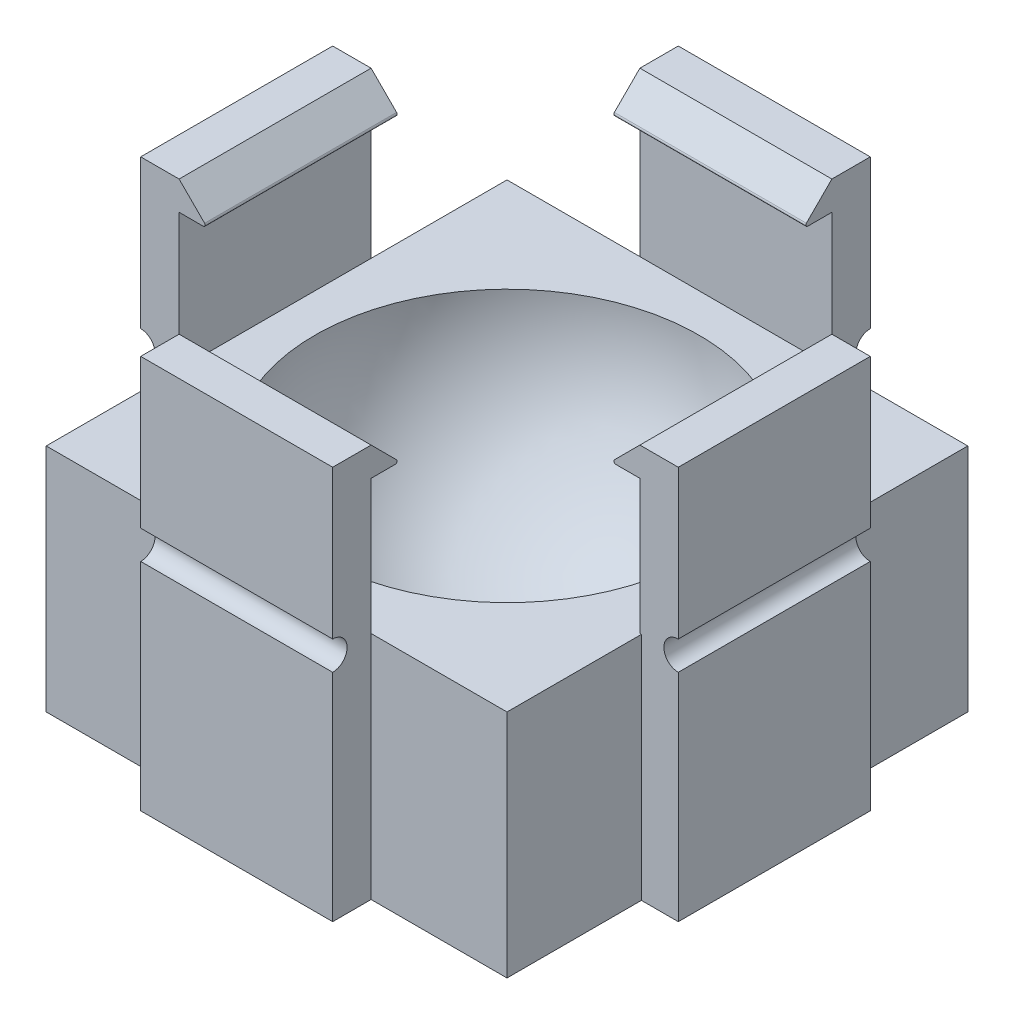
SolidWorks part; units mm, degrees
ref_plane "Front Plane" through (0, 0, 0) normal (0, 0, 1) x (1, 0, 0)
ref_plane "Top Plane" through (0, 0, 0) normal (0, 1, 0) x (1, 0, 0)
ref_plane "Right Plane" through (0, 0, 0) normal (1, 0, 0) x (0, 0, -1)
sketch "Sketch1" plane through (0, 0, 0) normal (0, 1, 0) x (1, 0, 0)
  line L1 (0, 0) -> (250, 0)
  line L2 (0, 0) -> (0, 250)
  line L3 (0, 250) -> (250, 250)
  line L4 (250, 0) -> (250, 250)
  dimension "D1" = 250
  dimension "D2" = 250
extrude "Boss-Extrude1" add sketch "Sketch1" along normal blind 5
sketch "Sketch2" plane through (0, 5, 0) normal (0, 1, 0) x (1, 0, 0)
  line L1 (113, 113) -> (137, 113)
  line L2 (113, 113) -> (113, 137)
  line L3 (113, 137) -> (137, 137)
  line L4 (137, 113) -> (137, 137)
  line L5 (113, 113) -> (137, 137) construction
  line L6 (113, 137) -> (137, 113) construction
  line L7 (0, 250) -> (0, 0) construction
  line L8 (250, 250) -> (0, 250) construction
  line L10 (221, 137) -> (221, 113)
  line L11 (221, 113) -> (245, 113)
  line L12 (245, 113) -> (245, 137)
  line L13 (245, 137) -> (221, 137)
  line L19 (137, 29.0789) -> (113, 29.0789)
  line L20 (113, 29.0789) -> (113, 5.0789)
  line L21 (113, 5.0789) -> (137, 5.0789)
  line L22 (137, 5.0789) -> (137, 29.0789)
  point P0 (125, 125)
  dimension "D1" = 24
  dimension "D2" = 24
  dimension "D3" = 125
  dimension "D4" = 125
extrude "Boss-Extrude2" add sketch "Sketch2" along normal blind 12
sketch "Sketch4" plane through (0, 17, 0) normal (0, 1, 0) x (1, 0, 0)
  line L0 (125, 135) -> (125, 115)
  line L1 (125, 7) -> (125, 27)
  line L3 (233, 135) -> (233, 115)
  arc A0 (125, 135) -> (125, 115) centre (125, 125) ccw
  arc A2 (125, 27) -> (125, 7) centre (125, 17) ccw
  arc A3 (233, 115) -> (233, 135) centre (233, 125) ccw
revolve "Cut-Revolve1" cut sketch "Sketch4" angle 360 about L0 region at (120.7559, 17, -125)
revolve "Cut-Revolve2" cut sketch "Sketch4<3>" angle 360 about L3
sketch "Sketch4<3>" plane through (0, 17, 0) normal (0, 1, 0) x (1, 0, 0) same geometry as "Sketch4"
revolve "Cut-Revolve3" cut sketch "Sketch4<4>" angle 360 about L1
sketch "Sketch4<4>" plane through (0, 17, 0) normal (0, 1, 0) x (1, 0, 0) same geometry as "Sketch4"
sketch "Sketch5" plane through (0, 5, 0) normal (0, 1, 0) x (1, 0, 0)
  line L8 (125, 137) -> (130, 137)
  line L9 (137, 137) -> (113, 137) construction
  line L10 (137, 137) -> (113, 137) construction
  line L11 (130, 137) -> (130, 139)
  line L12 (130, 139) -> (120, 139)
  line L13 (120, 139) -> (120, 137)
  line L14 (120, 137) -> (125, 137)
  line L15 (120, 113) -> (125, 113)
  line L16 (120, 111) -> (120, 113)
  line L17 (130, 111) -> (120, 111)
  line L18 (130, 113) -> (130, 111)
  line L19 (125, 113) -> (130, 113)
  line L21 (113, 29.0789) -> (113, 5.0789) construction
  line L22 (137, 5.0789) -> (137, 29.0789) construction
  line L24 (125, 29.0789) -> (130, 29.0789)
  line L25 (130, 29.0789) -> (130, 31.0789)
  line L26 (130, 31.0789) -> (120, 31.0789)
  line L27 (120, 31.0789) -> (120, 29.0789)
  line L28 (120, 29.0789) -> (125, 29.0789)
  line L29 (120, 5.0789) -> (125, 5.0789)
  line L30 (120, 3.0789) -> (120, 5.0789)
  line L31 (130, 3.0789) -> (120, 3.0789)
  line L32 (130, 5.0789) -> (130, 3.0789)
  line L33 (125, 5.0789) -> (130, 5.0789)
  line L36 (113, 130) -> (113, 125)
  line L37 (111, 130) -> (113, 130)
  line L38 (111, 120) -> (111, 130)
  line L39 (113, 120) -> (111, 120)
  line L40 (113, 125) -> (113, 120)
  line L41 (137, 125) -> (137, 120)
  line L42 (137, 120) -> (139, 120)
  line L43 (139, 120) -> (139, 130)
  line L44 (139, 130) -> (137, 130)
  line L45 (137, 130) -> (137, 125)
  line L46 (220.9211, 130) -> (220.9211, 125)
  line L47 (218.9211, 130) -> (220.9211, 130)
  line L48 (218.9211, 120) -> (218.9211, 130)
  line L49 (220.9211, 120) -> (218.9211, 120)
  line L50 (220.9211, 125) -> (220.9211, 120)
  line L51 (244.9211, 125) -> (244.9211, 120)
  line L52 (244.9211, 120) -> (246.9211, 120)
  line L53 (246.9211, 120) -> (246.9211, 130)
  line L54 (246.9211, 130) -> (244.9211, 130)
  line L55 (244.9211, 130) -> (244.9211, 125)
  line L56 (137, 12.0789) -> (137, 17.0789)
  line L57 (139, 12.0789) -> (137, 12.0789)
  line L58 (139, 22.0789) -> (139, 12.0789)
  line L59 (137, 22.0789) -> (139, 22.0789)
  line L60 (137, 17.0789) -> (137, 22.0789)
  line L61 (113, 17.0789) -> (113, 22.0789)
  line L62 (113, 22.0789) -> (111, 22.0789)
  line L63 (111, 22.0789) -> (111, 12.0789)
  line L64 (111, 12.0789) -> (113, 12.0789)
  line L65 (113, 12.0789) -> (113, 17.0789)
  line L66 (237.9211, 137) -> (232.9211, 137)
  line L67 (237.9211, 139) -> (237.9211, 137)
  line L68 (227.9211, 139) -> (237.9211, 139)
  line L69 (227.9211, 137) -> (227.9211, 139)
  line L70 (232.9211, 137) -> (227.9211, 137)
  line L71 (232.9211, 113) -> (227.9211, 113)
  line L72 (227.9211, 113) -> (227.9211, 111)
  line L73 (227.9211, 111) -> (237.9211, 111)
  line L74 (237.9211, 111) -> (237.9211, 113)
  line L75 (237.9211, 113) -> (232.9211, 113)
extrude "Boss-Extrude3" add sketch "Sketch5" along normal blind 19
sketch "Sketch8" plane through (120, 0, 0) normal (-1, 0, 0) x (0, 0, 1)
  line L0 (-3.0789, 24) -> (-6.5789, 24)
  line L1 (-3.0789, 24) -> (-3.0789, 25.5)
  line L2 (-3.0789, 25.5) -> (-5.0789, 25.5)
  line L3 (-5.0789, 25.5) -> (-6.5789, 24)
  line L8 (-29.0789, 25.5) -> (-27.5789, 24)
  line L9 (-31.0789, 25.5) -> (-29.0789, 25.5)
  line L10 (-31.0789, 24) -> (-31.0789, 25.5)
  line L11 (-31.0789, 24) -> (-27.5789, 24)
  line L12 (-111, 24) -> (-114.5, 24)
  line L13 (-111, 24) -> (-111, 25.5)
  line L14 (-111, 25.5) -> (-113, 25.5)
  line L15 (-113, 25.5) -> (-114.5, 24)
  line L16 (-137, 25.5) -> (-135.5, 24)
  line L17 (-139, 25.5) -> (-137, 25.5)
  line L18 (-139, 24) -> (-139, 25.5)
  line L19 (-139, 24) -> (-135.5, 24)
extrude "Boss-Extrude5" add sketch "Sketch8" against normal blind 10
sketch "Sketch9" plane through (0, 0, -130) normal (0, 0, -1) x (-1, 0, 0)
  line L0 (-111, 24) -> (-114.5, 24)
  line L1 (-111, 24) -> (-111, 25.5)
  line L2 (-111, 25.5) -> (-113, 25.5)
  line L3 (-113, 25.5) -> (-114.5, 24)
  line L8 (-137, 25.5) -> (-135.5, 24)
  line L9 (-139, 25.5) -> (-137, 25.5)
  line L10 (-139, 24) -> (-139, 25.5)
  line L11 (-139, 24) -> (-135.5, 24)
  line L12 (-218.9211, 24) -> (-222.4211, 24)
  line L13 (-218.9211, 24) -> (-218.9211, 25.5)
  line L14 (-218.9211, 25.5) -> (-220.9211, 25.5)
  line L15 (-220.9211, 25.5) -> (-222.4211, 24)
  line L16 (-244.9211, 25.5) -> (-243.4211, 24)
  line L17 (-246.9211, 25.5) -> (-244.9211, 25.5)
  line L18 (-246.9211, 24) -> (-246.9211, 25.5)
  line L19 (-246.9211, 24) -> (-243.4211, 24)
extrude "Boss-Extrude6" add sketch "Sketch9" against normal blind 10
sketch "Sketch10" plane through (237.9211, 0, 0) normal (1, 0, 0) x (0, 0, -1)
  line L0 (139, 24) -> (135.5, 24)
  line L1 (135.5, 24) -> (137, 25.5)
  line L2 (137, 25.5) -> (139, 25.5)
  line L3 (139, 25.5) -> (139, 24)
  line L8 (111, 25.5) -> (111, 24)
  line L9 (113, 25.5) -> (111, 25.5)
  line L10 (114.5, 24) -> (113, 25.5)
  line L11 (111, 24) -> (114.5, 24)
extrude "Boss-Extrude7" add sketch "Sketch10" against normal blind 10
sketch "Sketch11" plane through (0, 0, -12.0789) normal (0, 0, 1) x (1, 0, 0)
  line L0 (139, 24) -> (135.5, 24)
  line L1 (135.5, 24) -> (137, 25.5)
  line L2 (137, 25.5) -> (139, 25.5)
  line L3 (139, 25.5) -> (139, 24)
  line L6 (111, 25.5) -> (111, 24)
  line L7 (113, 25.5) -> (111, 25.5)
  line L8 (114.5, 24) -> (113, 25.5)
  line L9 (111, 24) -> (114.5, 24)
extrude "Boss-Extrude8" add sketch "Sketch11" against normal blind 10
sketch "Sketch12" plane through (0, 0, -12.0789) normal (0, 0, 1) x (1, 0, 0)
  line L0 (139, 25.5) -> (139, 5) construction
  line L1 (111, 25.5) -> (111, 5) construction
  circle A0 centre (139, 17) radius 0.75
  circle A1 centre (111, 17) radius 0.75
extrude "Cut-Extrude1" cut sketch "Sketch12" against normal through all
sketch "Sketch13" plane through (120, 0, 0) normal (-1, 0, 0) x (0, 0, 1)
  line L0 (-111, 25.5) -> (-111, 5) construction
  line L1 (-139, 25.5) -> (-139, 5) construction
  circle A0 centre (-111, 17) radius 0.75
  circle A1 centre (-139, 17) radius 0.75
extrude "Cut-Extrude2" cut sketch "Sketch13" against normal through all
sketch "Sketch14" plane through (0, 0, -130) normal (0, 0, -1) x (-1, 0, 0)
  line L0 (-218.9211, 25.5) -> (-218.9211, 5) construction
  line L1 (-246.9211, 25.5) -> (-246.9211, 5) construction
  circle A0 centre (-218.9211, 17) radius 0.75
  circle A1 centre (-246.9211, 17) radius 0.75
extrude "Cut-Extrude3" cut sketch "Sketch14" against normal through all
sketch "Sketch15" plane through (130, 0, 0) normal (1, 0, 0) x (0, 0, -1)
  line L0 (31.0789, 25.5) -> (31.0789, 5) construction
  line L1 (3.0789, 25.5) -> (3.0789, 5) construction
  circle A0 centre (31.0789, 17) radius 0.75
  circle A1 centre (3.0789, 17) radius 0.75
extrude "Cut-Extrude4" cut sketch "Sketch15" against normal through all
fillet "Fillet1" radius 0.1 12 edges at (232.9211, 24, -135.5) (243.4211, 24, -125) (232.9211, 24, -114.5) (222.4211, 24, -125) (114.5, 24, -125) (125, 24, -135.5) (125, 24, -114.5) (135.5, 24, -125) (135.5, 24, -17.0789) (125, 24, -6.5789) (114.5, 24, -17.0789) (125, 24, -27.5789)
sketch "Sketch17" plane through (0, 0, 0) normal (0, -1, 0) x (1, 0, 0)
  line L0 (124.65, -235) -> (125.35, -235) construction
  line L1 (250, -250) -> (0, -250) construction
  line L2 (125, -125) -> (0, -250)
  line L3 (125, -250) -> (125, -235)
  line L4 (124.65, -232.7) -> (125.35, -232.7)
  line L5 (124.65, -237.3) -> (125.35, -237.3)
  line L6 (15, -125.35) -> (15, -124.65) construction
  line L7 (17.3, -125.35) -> (17.3, -124.65)
  line L8 (12.7, -125.35) -> (12.7, -124.65)
  arc A0 (124.65, -232.7) -> (124.65, -237.3) centre (124.65, -235) ccw
  arc A1 (125.35, -237.3) -> (125.35, -232.7) centre (125.35, -235) ccw
  arc A2 (17.3, -125.35) -> (12.7, -125.35) centre (15, -125.35) cw
  arc A3 (12.7, -124.65) -> (17.3, -124.65) centre (15, -124.65) cw
  point P9 (125, -235)
  point P16 (15, -125)
  dimension "D1" = 0.7
  dimension "D2" = 4.6
extrude "Cut-Extrude5" cut sketch "Sketch17" against normal blind 2.3 contours L5 A1 L4 A0 | A3 L8 A2 L7 region at (125, 0, -232.7702) region at (15, 0, -125)
sketch "Sketch18" plane through (0, 2.3, 0) normal (0, -1, 0) x (1, 0, 0)
  line L0 (0, -250) -> (125, -125)
  line L1 (17.1564, -123.85) -> (12.8436, -123.85)
  line L2 (17.1564, -126.15) -> (12.8436, -126.15)
  line L3 (123.85, -232.8436) -> (123.85, -237.1564)
  line L4 (126.15, -232.8436) -> (126.15, -237.1564)
  line L6 (123.85, -231.5086) -> (123.85, -238.4914) construction
  line L7 (126.15, -231.5086) -> (126.15, -238.4914) construction
  line L8 (124.65, -232.7) -> (124.65, -237.3) construction
  line L9 (125.35, -232.7) -> (125.35, -237.3) construction
  arc A0 (123.85, -232.8436) -> (123.85, -237.1564) centre (124.65, -235) ccw
  arc A1 (126.15, -237.1564) -> (126.15, -232.8436) centre (125.35, -235) ccw
  arc A2 (12.8436, -123.85) -> (17.1564, -123.85) centre (15, -124.65) cw
  arc A3 (124.65, -232.7) -> (124.65, -237.3) centre (124.65, -235) ccw construction
  arc A4 (125.35, -237.3) -> (125.35, -232.7) centre (125.35, -235) ccw construction
  arc A5 (123.85, -238.4914) -> (123.85, -231.5086) centre (125.35, -235) ccw construction
  arc A6 (126.15, -231.5086) -> (126.15, -238.4914) centre (124.65, -235) ccw construction
  arc A7 (17.1564, -126.15) -> (12.8436, -126.15) centre (15, -125.35) cw
  arc M2 (125.35, -237.3) -> (125.35, -232.7) centre (125.35, -235) ccw
  arc M4 (124.65, -232.7) -> (124.65, -237.3) centre (124.65, -235) ccw
  dimension "D1" = 1.5
extrude "Cut-Extrude6" cut sketch "Sketch18" against normal through all contours L3 M4 | L4 M2 | A7 L2 | A2 L1 region at (15, 2.3, -123.2293) region at (15, 2.3, -126.7707) region at (123.2293, 2.3, -235) region at (126.7707, 2.3, -235)
sketch "Sketch19" plane through (0, 0, 0) normal (0, 0, 1) x (1, 0, 0)
  line L0 (120, 5) -> (130, 5) construction
  line L1 (120, 5) -> (121, 5)
  line L2 (129, 5) -> (130, 5)
  arc A0 (130, 5) -> (120, 5) centre (125, 5) ccw
  arc A1 (129, 5) -> (121, 5) centre (125, 5) ccw
extrude "Boss-Extrude9" add sketch "Sketch19" against normal blind 80 from offset 150 offset against normal yes
sketch "Sketch20" plane through (0, 0, 0) normal (1, 0, 0) x (0, 0, -1)
  line L0 (0, 5) -> (250, 5) construction
  line L1 (120, 5) -> (121, 5)
  line L2 (129, 5) -> (130, 5)
  arc A0 (130, 5) -> (120, 5) centre (125, 5) ccw
  arc A1 (129, 5) -> (121, 5) centre (125, 5) ccw
extrude "Boss-Extrude10" add sketch "Sketch20" along normal blind 40 from offset 20
sketch "Sketch21" plane through (0, 5, 0) normal (0, 1, 0) x (1, 0, 0)
  line L0 (85.2046, 138.5) -> (65.6046, 138.5)
  line L1 (85.2046, 135.5) -> (68.6046, 135.5)
  line L2 (68.6046, 135.5) -> (68.6046, 114.5)
  line L3 (68.6046, 114.5) -> (85.2046, 114.5)
  line L4 (65.6046, 138.5) -> (65.6046, 111.5)
  line L5 (65.6046, 111.5) -> (85.2046, 111.5)
  line L6 (85.2046, 138.5) -> (85.2046, 135.5)
  line L8 (85.2046, 114.5) -> (85.2046, 122.5)
  line L9 (85.2046, 122.5) -> (88.2046, 122.5)
  line L10 (88.2046, 122.5) -> (88.2046, 111.5)
  line L11 (88.2046, 111.5) -> (85.2046, 111.5)
  dimension "D1" = 3
extrude "Boss-Extrude11" add sketch "Sketch21" along normal blind 6
sketch "Sketch22" plane through (0, 11, 0) normal (0, 1, 0) x (1, 0, 0)
  line L1 (65.6046, 138.5) -> (88.2046, 138.5)
  line L2 (65.6046, 138.5) -> (65.6046, 111.5)
  line L3 (65.6046, 111.5) -> (88.2046, 111.5)
  line L4 (88.2046, 138.5) -> (88.2046, 111.5)
extrude "Boss-Extrude12" add sketch "Sketch22" along normal blind 2
sketch "Sketch23" plane through (0, 13, 0) normal (0, 1, 0) x (1, 0, 0)
  line L0 (88.2046, 122.5) -> (85.2046, 122.5)
  line L1 (85.2046, 122.5) -> (85.2046, 114.5)
  line L2 (85.2046, 114.5) -> (88.2046, 114.5)
  line L3 (88.2046, 111.5) -> (88.2046, 138.5) construction
  line L4 (88.2046, 114.5) -> (88.2046, 122.5)
extrude "Cut-Extrude7" cut sketch "Sketch23" against normal blind 4 from offset 4 offset against normal yes
sketch "Sketch24" plane through (65.6046, 0, 0) normal (-1, 0, 0) x (0, 0, 1)
  line L0 (-138.5, 5) -> (-111.5, 5) construction
  line L1 (-127, 5) -> (-123, 5)
  arc A0 (-123, 5) -> (-127, 5) centre (-125, 5) ccw
extrude "Cut-Extrude8" cut sketch "Sketch24" against normal blind 6
sketch "Sketch26" plane through (0, 5, 0) normal (0, 1, 0) x (1, 0, 0)
  line L0 (111, 120) -> (111, 130) construction
  line L1 (111, 130) -> (111, 128)
  line L2 (111, 122) -> (111, 120)
  arc A0 (111, 130) -> (111, 120) centre (111, 125) ccw
  arc A1 (111, 128) -> (111, 122) centre (111, 125) ccw
extrude "Boss-Extrude13" add sketch "Sketch26" along normal blind 3 from offset 5
sketch "Sketch27" plane through (0, 5, 0) normal (0, 1, 0) x (1, 0, 0)
  line L0 (130, 139) -> (120, 139) construction
  line L1 (120, 139) -> (122, 139)
  line L2 (128, 139) -> (130, 139)
  arc A0 (130, 139) -> (120, 139) centre (125, 139) ccw
  arc A1 (128, 139) -> (122, 139) centre (125, 139) ccw
extrude "Boss-Extrude14" add sketch "Sketch27" along normal blind 3 from offset 5
sketch "Sketch28" plane through (0, 5, 0) normal (0, 1, 0) x (1, 0, 0)
  line L0 (250, 0) -> (250, 250) construction
  line L1 (250, 96.238) -> (194.5231, 96.238)
  line L3 (250, 149.4756) -> (194.5231, 149.4756)
  line L4 (194.5231, 96.238) -> (194.5231, 149.4756)
  line L7 (250, 0) -> (0, 0)
  line L8 (250, 0) -> (250, 250)
  line L9 (250, 250) -> (0, 250)
  line L10 (0, 0) -> (0, 250)
extrude "Cut-Extrude9" cut sketch "Sketch28" against normal through all and the other way through all contours L10 L7 L8 L1 L4 L3 L9 region at (120.1759, 5, -125.1063)
sketch "Sketch29" plane through (0, 0, -149.4756) normal (0, 0, -1) x (-1, 0, 0)
  line L1 (-250, 5) -> (-194.5231, 5)
  line L2 (-250, 5) -> (-250, 0)
  line L3 (-250, 0) -> (-194.5231, 0)
  line L4 (-194.5231, 5) -> (-194.5231, 0)
extrude "Cut-Extrude10" cut sketch "Sketch29" against normal through all
